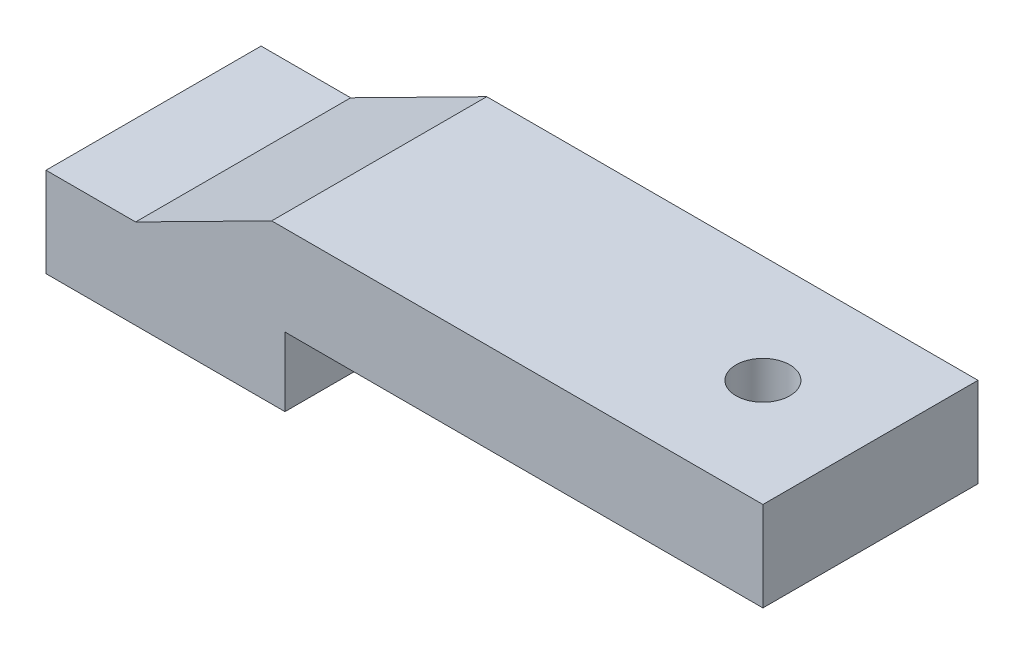
SolidWorks part; units mm, degrees
material "Acrylic (Medium-high impact)"
ref_plane "Front Plane" through (0, 0, 0) normal (0, 0, 1) x (1, 0, 0)
ref_plane "Top Plane" through (0, 0, 0) normal (0, 1, 0) x (1, 0, 0)
ref_plane "Right Plane" through (0, 0, 0) normal (1, 0, 0) x (0, 0, -1)
sketch "Sketch1" plane through (0, 0, 0) normal (0, 0, 1) x (1, 0, 0)
  line L0 (-70.9627, -26.5468) -> (-30.9627, -26.5468)
  line L1 (-30.9627, -26.5468) -> (-30.9627, -15.6889)
  line L3 (-29.6039, -15) -> (0.4965, -15)
  line L4 (0.4965, -15) -> (49.0373, -15)
  line L5 (49.0373, -15) -> (49.0373, 0)
  line L6 (49.0373, 0) -> (-33.1894, 0)
  line L7 (-33.1894, 0) -> (-55.9627, -11.5468)
  line L8 (-55.9627, -11.5468) -> (-70.9627, -11.5468)
  line L9 (-70.9627, -11.5468) -> (-70.9627, -26.5468)
  line L10 (-30.9627, -15.6889) -> (-30.9627, -15)
  line L11 (-30.9627, -15) -> (-29.6039, -15)
  dimension "D1" = 40
  dimension "D2" = 15
  dimension "D4" = 15
  dimension "D5" = 120
  dimension "D6" = 15
extrude "Boss-Extrude1" add sketch "Sketch1" along normal blind 36
sketch "Sketch2" plane through (0, 0, 0) normal (0, 1, 0) x (1, 0, 0)
  line L0 (49.0373, 0) -> (13.0373, -36) construction
  line L1 (49.0373, -36) -> (-33.1894, -36) construction
  line L2 (13.0373, -36) -> (49.0373, -36) construction
  line L3 (49.0373, -36) -> (15.8679, -2.8305) construction
  circle A0 centre (31.0373, -18) radius 4.5
  dimension "D1" = 9
extrude "Cut-Extrude1" cut sketch "Sketch2" against normal blind 30
